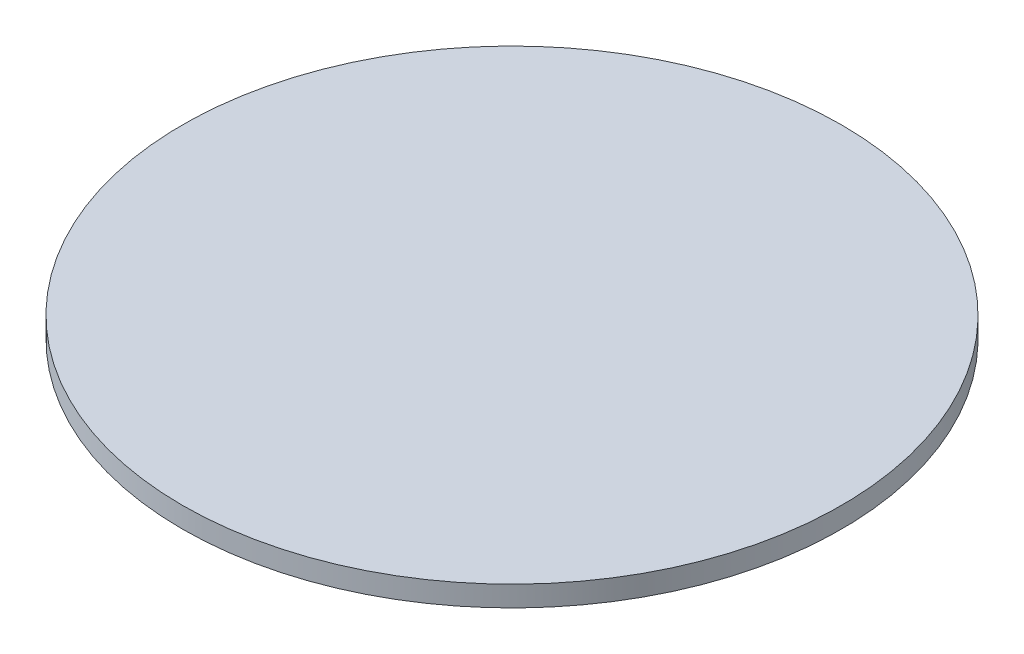
SolidWorks part; units mm, degrees
ref_plane "Front" through (0, 0, 0) normal (0, 0, 1) x (1, 0, 0)
ref_plane "Top" through (0, 0, 0) normal (0, 1, 0) x (1, 0, 0)
ref_plane "Right" through (0, 0, 0) normal (1, 0, 0) x (0, 0, -1)
sketch "Sketch1" plane through (0, 0, 0) normal (0, 1, 0) x (1, 0, 0)
  circle A0 centre (0, 0) radius 101.6
  dimension "D1" = 203.2
extrude "Boss-Extrude1" add sketch "Sketch1" against normal blind 6.35
